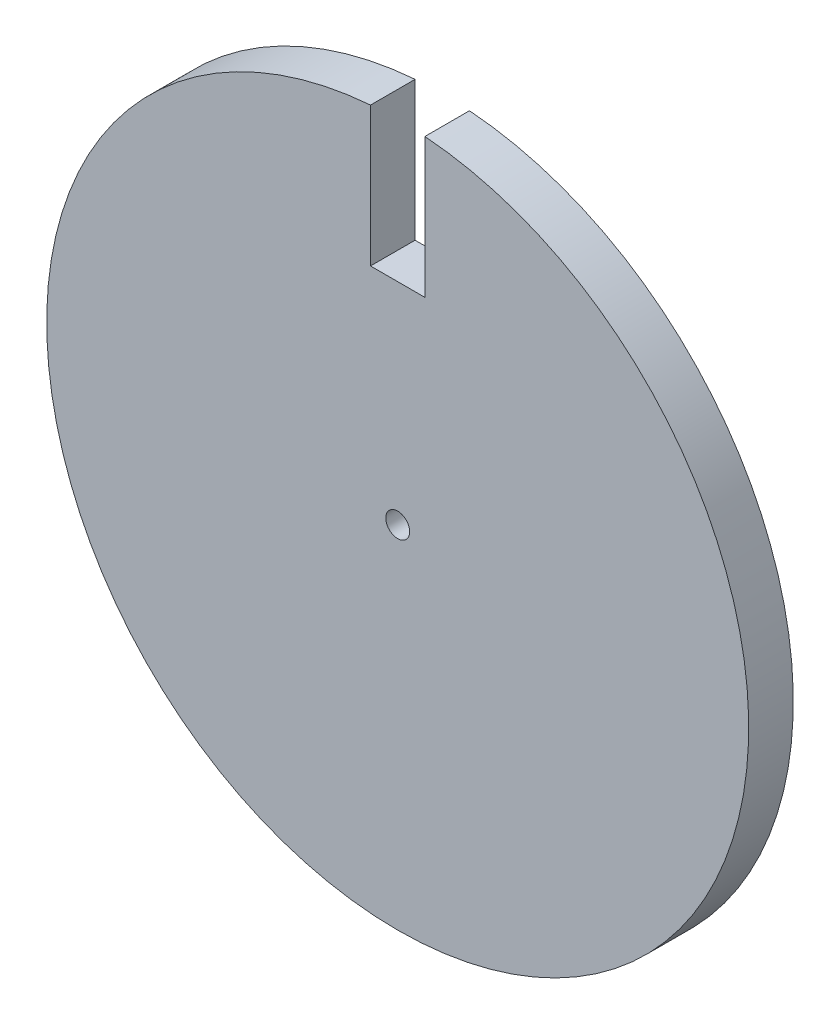
SolidWorks part; units mm, degrees
ref_plane "Front Plane" through (0, 0, 0) normal (0, 0, 1) x (1, 0, 0)
ref_plane "Top Plane" through (0, 0, 0) normal (0, 1, 0) x (1, 0, 0)
ref_plane "Right Plane" through (0, 0, 0) normal (1, 0, 0) x (0, 0, -1)
sketch "Sketch1" plane through (0, 0, 0) normal (0, 0, 1) x (1, 0, 0)
  circle A0 centre (0, 0) radius 25
  circle A1 centre (0, 0) radius 0.85
  dimension "D1" = 1.7
  dimension "D2" = 50
extrude "Boss-Extrude1" add sketch "Sketch1" along normal blind 3.175
sketch "Sketch2" plane through (0, 0, 0) normal (0, 0, -1) x (-1, 0, 0)
  line L0 (0, 0) -> (0, 25) construction
  line L1 (1.937, 34.0448) -> (-1.937, 34.0448)
  line L2 (-1.937, 34.0448) -> (-1.937, 15)
  line L3 (-1.937, 15) -> (1.937, 15)
  line L4 (1.937, 15) -> (1.937, 34.0448)
  circle A0 centre (0, 0) radius 25 construction
  point P9 (0, 34.0448)
  dimension "D1" = 15
extrude "Cut-Extrude1" cut sketch "Sketch2" against normal up to body separate body
